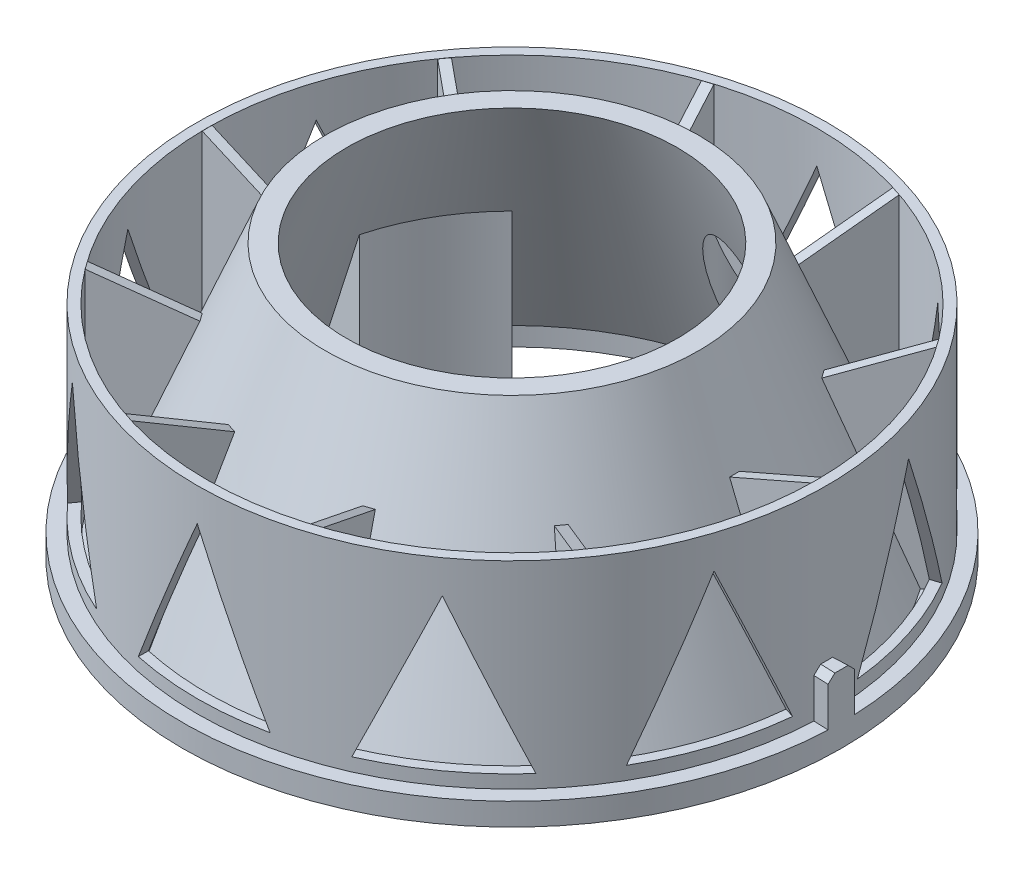
SolidWorks part; units mm, degrees
material "ABS"
ref_plane "Спереди" through (0, 0, 0) normal (0, 0, 1) x (1, 0, 0)
ref_plane "Сверху" through (0, 0, 0) normal (0, 1, 0) x (1, 0, 0)
ref_plane "Справа" through (0, 0, 0) normal (1, 0, 0) x (0, 0, -1)
sketch "Эскиз1" plane through (0, 0, 0) normal (0, 0, 1) x (1, 0, 0)
  line L0 (0, 0) -> (0, 41.0099) construction
  line L1 (46.25, 35) -> (47.75, 35)
  line L2 (46.25, 3) -> (46.25, 35)
  line L3 (50, 0) -> (50, 5)
  line L4 (50, 5) -> (47.75, 5)
  line L5 (47.75, 5) -> (47.75, 35)
  line L6 (41.25, 3) -> (25.089, 43)
  line L7 (46.25, 3) -> (44.4856, 3)
  line L8 (-48, 3) -> (48, 3) construction
  line L9 (50, 0) -> (32.75, 0)
  line L10 (32.75, 0) -> (32.75, 3)
  line L11 (44.4856, 3) -> (28.3246, 43)
  line L12 (25.089, 43) -> (28.3246, 43)
  line L13 (-33.0727, 17.1849) -> (32.9273, 17.1849) construction
  line L14 (32.75, 3) -> (-29.7958, 3) construction
  line L17 (41.25, 3) -> (32.75, 3)
  circle A0 centre (0, 17.1849) radius 33 construction
  dimension "D5" = 3
  dimension "D8" = 68
  dimension "D9" = 66
  dimension "D1" = 50
  dimension "D2" = 2.25
  dimension "D3" = 1.5
  dimension "D4" = 5
  dimension "D6" = 30
  dimension "D7" = 8.5
  dimension "D10" = 40
  dimension "D11" = 17.25
  dimension "D12" = 32.75
  dimension "D13" = 47.75
revolve "Повернуть1" add sketch "Эскиз1" angle 360 about L0
sketch "Эскиз2" plane through (0, 0, 0) normal (0, 0, 1) x (1, 0, 0)
  line L0 (46.3265, 35) -> (33.755, 29.5084)
  line L1 (47.75, 35) -> (-47.75, 35) construction
  line L2 (33.755, 29.5084) -> (44.4256, 2.3778)
  line L3 (44.4256, 2.3778) -> (46.3265, 2.3778)
  line L4 (46.3265, 2.3778) -> (46.3265, 35)
extrude "Ребро" add sketch "Эскиз2" along normal mid plane 1.5
pattern_circular "Массив ребер" count 10 over 360 about axis through (0, 0, 0) along (0, 1, 0) of "Ребро"
sketch "Эскиз3" plane through (0, 0, 0) normal (0, 1, 0) x (1, 0, 0)
  line L1 (0, 0) -> (0, 41.0716) construction
  circle A0 centre (0, 36) radius 5
  circle A3 centre (0, 0) radius 36 construction
  dimension "D1" = 10
  dimension "D2" = 72
extrude "Вырез под РМО" cut sketch "Эскиз3" against normal blind 24.5 and the other way blind 37.9
sketch "Эскиз4" plane through (0, 0, 0) normal (0, 1, 0) x (1, 0, 0)
  line L0 (0, 0) -> (-25, 43.3013) construction
  line L1 (0, 0) -> (-29.3449, 29.3449)
  line L2 (0, 0) -> (-63.5782, 0) construction
  line L3 (-10.741, 40.0859) -> (0, 0)
  circle A0 centre (0, 0) radius 50 construction
  arc A1 (-29.3449, 29.3449) -> (-10.741, 40.0859) centre (0, 0) cw
  point P8 (-20.75, 35.9401)
  dimension "D1" = 41.5
  dimension "D2" = 30
  dimension "60" = 60
extrude "Вырез под РД" cut sketch "Эскиз4" along normal up to surface (3 mm away) up to face at (0, 3, -4.125)
pattern_circular "Круговой массив2" count 6 over 360 about axis through (0, 0, 0) along (0, 1, 0) of "Вырез под РД"
sketch "Эскиз5" plane through (0, 0, 0) normal (0, 0, 1) x (1, 0, 0)
  line L0 (-10, 7) -> (0, 30)
  line L1 (-10, 7) -> (10, 7)
  line L2 (-10, 7) -> (-10, 30) construction
  line L3 (-10, 30) -> (10, 30) construction
  line L4 (10, 7) -> (10, 30) construction
  line L5 (-10, 7) -> (10, 30) construction
  line L6 (-10, 30) -> (10, 7) construction
  line L7 (0, 30) -> (10, 7)
  line L8 (50, 5) -> (-50, 5) construction
  line L9 (47.75, 35) -> (-47.75, 35) construction
  point P0 (0, 18.5)
  dimension "D1" = 5
  dimension "D2" = 20
  dimension "D3" = 2
extrude "Вырез-Вытянуть1" cut sketch "Эскиз5" along normal up to surface (1.5352 mm away) from surface
pattern_circular "Круговой массив3" count 10 over 360 about axis through (0, 0, 0) along (0, 1, 0) of "Вырез-Вытянуть1"
sketch "Эскиз7" plane through (0, 5, 0) normal (0, 1, 0) x (1, 0, 0)
  line L0 (0, 0) -> (50, 0) construction
  line L1 (47.7118, 1.91) -> (49.96, 2)
  line L2 (47.7118, -1.91) -> (49.96, -2)
  circle A0 centre (0, 0) radius 47.75 construction
  circle A1 centre (0, 0) radius 50
  circle A2 centre (0, 0) radius 50
  circle A3 centre (0, 0) radius 47.75
  circle M5 centre (0, 0) radius 47.75
  circle M6 centre (0, 0) radius 50
  dimension "D2" = 4
  dimension "D1" = 0
extrude "Бобышка-Вытянуть1" add sketch "Эскиз7" along normal blind 7 contours L0 A2 L1 M5 | L0 A3 L2 M6
chamfer "Фаска1" distance 1 angle 45 2 edges at (48.8359, 12, 1.955) (48.8359, 12, -1.955)
sketch "Эскиз8" plane through (0, 0, 0) normal (0, -1, 0) x (1, 0, 0)
  circle A1 centre (0, 0) radius 45
  circle A2 centre (0, 0) radius 50 construction
  circle A3 centre (0, 0) radius 50
  dimension "D1" = 90
extrude "Вырез-Вытянуть2" cut sketch "Эскиз8" against normal blind 1.6
sketch "Эскиз9" plane through (0, 3, 0) normal (0, 1, 0) x (1, 0, 0)
  line L2 (31.6341, 8.4763) -> (39.8444, 10.6763)
  line L3 (29.1682, 29.1682) -> (23.1577, 23.1577)
  line L4 (31.6341, 8.4763) -> (39.8444, 10.6763)
  line L5 (29.1682, 29.1682) -> (23.1577, 23.1577)
  arc A2 (31.6341, 8.4763) -> (23.1577, 23.1577) centre (0, 0) ccw
  arc A3 (39.8444, 10.6763) -> (29.1682, 29.1682) centre (0, 0) ccw
  arc A4 (31.6341, 8.4763) -> (23.1577, 23.1577) centre (0, 0) ccw
  arc A5 (39.8444, 10.6763) -> (29.1682, 29.1682) centre (0, 0) ccw
  dimension "D1" = 0
extrude "Бобышка-Вытянуть2" add sketch "Эскиз9" along normal up to surface (21.0382 mm away)
pattern_circular "Круговой массив4" count 3 over 360 about axis through (0, 0, 0) along (0, -1, 0) of "Бобышка-Вытянуть2"
sketch "Эскиз10" plane through (0, 0, 0) normal (0, -1, 0) x (1, 0, 0)
  circle A0 centre (0, 0) radius 37.5
  circle A2 centre (0, 37.5) radius 2.2
  dimension "D1" = 75
  dimension "D2" = 4.4
extrude "Вырез-Вытянуть3" cut sketch "Эскиз10" against normal blind 12 contours A0 A2 | A0 A2
chamfer "Фаска2" distance 1 angle 45 1 edges at (0, 0, 35.3)
pattern_circular "Круговой массив5" count 3 over 360 about axis through (0, 0, 0) along (0, 1, 0) of "Вырез-Вытянуть3", "Фаска2"
chamfer "Фаска3" distance 0.4 angle 45 1 edges at (0, 0, -45)
